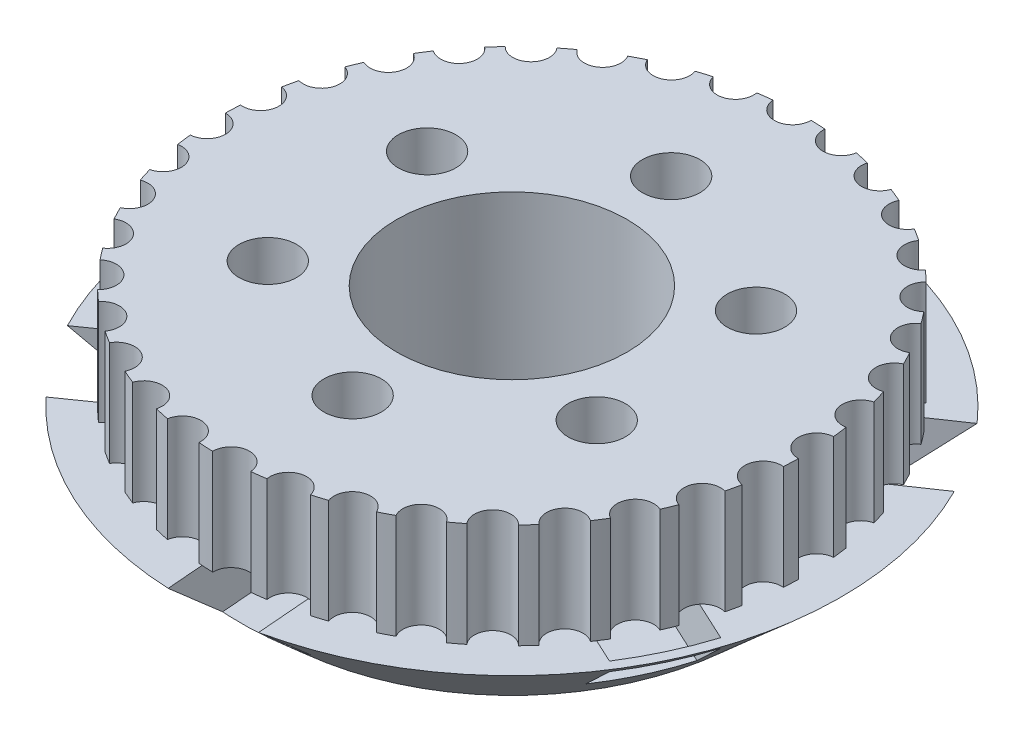
SolidWorks part; units mm, degrees
ref_plane "Front Plane" through (0, 0, 0) normal (0, 0, 1) x (1, 0, 0)
ref_plane "Top Plane" through (0, 0, 0) normal (0, 1, 0) x (1, 0, 0)
ref_plane "Right Plane" through (0, 0, 0) normal (1, 0, 0) x (0, 0, -1)
sketch "Sketch1" plane through (0, 0, 0) normal (0, 1, 0) x (1, 0, 0)
  circle A0 centre (0, 0) radius 28
  circle A1 centre (0, 0) radius 16.75 construction
  circle A2 centre (0, 0) radius 11
  circle A3 centre (-1.4643, 16.6859) radius 2.75
  circle A4 centre (13.7182, 9.611) radius 2.75
  circle A5 centre (15.1825, -7.0748) radius 2.75
  circle A6 centre (1.4643, -16.6859) radius 2.75
  circle A7 centre (-13.7182, -9.611) radius 2.75
  circle A8 centre (-15.1825, 7.0748) radius 2.75
  circle A9 centre (-24.8012, 12.9961) radius 1.75
  circle A10 centre (-22.1677, 17.1054) radius 1.75
  circle A11 centre (-18.8606, 20.6949) radius 1.75
  circle A12 centre (-14.9804, 23.6556) radius 1.75
  circle A13 centre (-10.6451, 25.8975) radius 1.75
  circle A14 centre (-5.9863, 27.3526) radius 1.75
  circle A15 centre (-1.1456, 27.9766) radius 1.75
  circle A16 centre (3.7298, 27.7505) radius 1.75
  circle A17 centre (8.492, 26.6812) radius 1.75
  circle A18 centre (12.9961, 24.8012) radius 1.75
  circle A19 centre (17.1054, 22.1677) radius 1.75
  circle A20 centre (20.6949, 18.8606) radius 1.75
  circle A21 centre (23.6556, 14.9804) radius 1.75
  circle A22 centre (25.8975, 10.6451) radius 1.75
  circle A23 centre (27.3526, 5.9863) radius 1.75
  circle A24 centre (27.9766, 1.1456) radius 1.75
  circle A25 centre (27.7505, -3.7298) radius 1.75
  circle A26 centre (26.6812, -8.492) radius 1.75
  circle A27 centre (24.8012, -12.9961) radius 1.75
  circle A28 centre (22.1677, -17.1054) radius 1.75
  circle A29 centre (18.8606, -20.6949) radius 1.75
  circle A30 centre (14.9804, -23.6556) radius 1.75
  circle A31 centre (10.6451, -25.8975) radius 1.75
  circle A32 centre (5.9863, -27.3526) radius 1.75
  circle A33 centre (1.1456, -27.9766) radius 1.75
  circle A34 centre (-3.7298, -27.7505) radius 1.75
  circle A35 centre (-8.492, -26.6812) radius 1.75
  circle A36 centre (-12.9961, -24.8012) radius 1.75
  circle A37 centre (-17.1054, -22.1677) radius 1.75
  circle A38 centre (-20.6949, -18.8606) radius 1.75
  circle A39 centre (-23.6556, -14.9804) radius 1.75
  circle A40 centre (-25.8975, -10.6451) radius 1.75
  circle A41 centre (-27.3526, -5.9863) radius 1.75
  circle A42 centre (-27.9766, -1.1456) radius 1.75
  circle A43 centre (-27.7505, 3.7298) radius 1.75
  circle A44 centre (-26.6812, 8.492) radius 1.75
  circle A45 centre (0, 0) radius 23 construction
  circle A46 centre (0, 0) radius 20 construction
  dimension "D1" = 56
  dimension "D2" = 22
  dimension "D3" = 33.5
  dimension "D4" = 5.5
  dimension "D6" = 3.5
  dimension "D8" = 46
  dimension "D9" = 40
  dimension "D5" = 6
  dimension "D7" = 36
extrude "Boss-Extrude1" add sketch "Sketch1" along normal blind 10 contours A44 A0 A43 A42 A41 A40 A39 A38 A37 A36 A35 A34 A33 A32 A31 A30 A29 A28 A27 A26 A25 A24 A23 A22 A21 A20 A19 region at (25.4369, 0, -1.0416)
sketch "Sketch2" plane through (0, 0, 0) normal (0, -1, 0) x (1, 0, 0)
  circle A1 centre (0, 0) radius 31.5
  circle A2 centre (0, 0) radius 11
  dimension "D1" = 63
  dimension "D2" = 22
ref_plane "Plane1" through (0, -8, 0) normal (0, -1, 0) x (-1, 0, 0)
sketch "Sketch4" plane through (0, 0, 0) normal (0, 1, 0) x (1, 0, 0)
  line L0 (-13.7182, -9.611) -> (-11.4231, -12.887)
  line L4 (-16.0134, -6.335) -> (-13.7182, -9.611)
  line L5 (-13.7182, -9.611) -> (-15.2116, -10.6573) construction
  line L6 (-6.0971, -9.1556) -> (-22.4771, -20.6315)
  line L7 (-10.6874, -2.6036) -> (-27.0674, -14.0795)
  line L8 (-10.9776, 0.7024) -> (-29.1059, 9.15)
  line L9 (-7.5985, 7.9538) -> (-25.7269, 16.4013)
  line L10 (-4.8805, 9.858) -> (-6.6289, 29.7815)
  line L11 (3.0889, 10.5574) -> (1.3405, 30.4808)
  line L12 (6.0971, 9.1556) -> (22.4771, 20.6315)
  line L13 (10.6874, 2.6036) -> (27.0674, 14.0795)
  line L14 (10.9776, -0.7024) -> (29.1059, -9.15)
  line L15 (7.5985, -7.9538) -> (25.7269, -16.4013)
  line L16 (4.8805, -9.858) -> (6.6289, -29.7815)
  line L17 (-3.0889, -10.5574) -> (-1.3405, -30.4808)
  line L18 (-5.6566, 18.7021) -> (-5.2413, 13.9703) construction
  line L19 (-5.449, 16.3362) -> (2.5204, 17.0356) construction
  line L20 (-1.4643, 16.6859) -> (0, 0) construction
  line L21 (-5.2413, 13.9703) -> (-1.0327, 11.768)
  line L22 (-5.6566, 18.7021) -> (-1.8959, 21.6037) construction
  line L23 (2.3128, 19.4015) -> (-1.8959, 21.6037) construction
  line L24 (2.3128, 19.4015) -> (2.728, 14.6696) construction
  line L25 (2.728, 14.6696) -> (-1.0327, 11.768)
  line L26 (17.7538, 7.5544) -> (13.8635, 4.8288) construction
  line L27 (13.1634, 14.1064) -> (9.2732, 11.3808) construction
  line L28 (13.1634, 14.1064) -> (17.5567, 12.3003) construction
  line L29 (17.7538, 7.5544) -> (17.5567, 12.3003) construction
  line L30 (13.8635, 4.8288) -> (9.4703, 6.6349)
  line L31 (9.2732, 11.3808) -> (9.4703, 6.6349)
  line L32 (15.2144, -11.7415) -> (10.9089, -9.7352) construction
  line L33 (18.5934, -4.4902) -> (14.2879, -2.4839) construction
  line L34 (18.5934, -4.4902) -> (19.2259, -9.1979) construction
  line L35 (15.2144, -11.7415) -> (19.2259, -9.1979) construction
  line L36 (10.9089, -9.7352) -> (10.2764, -5.0275)
  line L37 (14.2879, -2.4839) -> (10.2764, -5.0275)
  line L38 (-2.766, -19.1903) -> (-3.1812, -14.4585) construction
  line L39 (5.2034, -18.4909) -> (4.7881, -13.7591) construction
  line L40 (5.2034, -18.4909) -> (1.4426, -21.3925) construction
  line L41 (-2.766, -19.1903) -> (1.4426, -21.3925) construction
  line L42 (-3.1812, -14.4585) -> (0.5795, -11.5568)
  line L43 (4.7881, -13.7591) -> (0.5795, -11.5568)
  line L44 (-18.207, -7.3432) -> (-14.3168, -4.6176) construction
  line L45 (-13.6167, -13.8952) -> (-9.7264, -11.1696) construction
  line L46 (-13.6167, -13.8952) -> (-18.0099, -12.0891) construction
  line L47 (-18.207, -7.3432) -> (-18.0099, -12.0891) construction
  line L48 (-14.3168, -4.6176) -> (-9.9235, -6.4237)
  line L49 (-9.7264, -11.1696) -> (-9.9235, -6.4237)
  line L50 (-15.6676, 11.9527) -> (-11.3621, 9.9464) construction
  line L51 (-19.0466, 4.7013) -> (-14.7412, 2.695) construction
  line L52 (-19.0466, 4.7013) -> (-19.6791, 9.409) construction
  line L53 (-15.6676, 11.9527) -> (-19.6791, 9.409) construction
  line L54 (-11.3621, 9.9464) -> (-10.7296, 5.2387)
  line L55 (-14.7412, 2.695) -> (-10.7296, 5.2387)
  circle A0 centre (0, 0) radius 16.75 construction
  arc A1 (-25.7269, 16.4013) -> (-29.1059, 9.15) centre (0, 0) ccw
  arc A2 (-7.5985, 7.9538) -> (-10.9776, 0.7024) centre (0, 0) ccw
  arc A3 (1.3405, 30.4808) -> (-6.6289, 29.7815) centre (0, 0) ccw
  circle A5 centre (0, 0) radius 11 construction
  arc A6 (-10.6874, -2.6036) -> (-6.0971, -9.1556) centre (0, 0) ccw
  arc A7 (-27.0674, -14.0795) -> (-22.4771, -20.6315) centre (0, 0) ccw
  arc A8 (3.0889, 10.5574) -> (-4.8805, 9.858) centre (0, 0) ccw
  arc A9 (27.0674, 14.0795) -> (22.4771, 20.6315) centre (0, 0) ccw
  arc A10 (10.6874, 2.6036) -> (6.0971, 9.1556) centre (0, 0) ccw
  arc A11 (25.7269, -16.4013) -> (29.1059, -9.15) centre (0, 0) ccw
  arc A12 (7.5985, -7.9538) -> (10.9776, -0.7024) centre (0, 0) ccw
  arc A13 (-1.3405, -30.4808) -> (6.6289, -29.7815) centre (0, 0) ccw
  arc A14 (-3.0889, -10.5574) -> (4.8805, -9.858) centre (0, 0) ccw
  circle A16 centre (-1.4643, 16.6859) radius 2.75 construction
  circle A17 centre (-1.4643, 16.6859) radius 2.75
  point P48 (0, 0)
  point P49 (0, 0)
  dimension "D1" = 4
  dimension "D2" = 20
  dimension "D4" = 2.375
  dimension "D5" = 4.75
  dimension "D3" = 6
  dimension "D6" = 6
sketch "Sketch3" plane through (0, -8, 0) normal (0, -1, 0) x (-1, 0, 0)
  circle A0 centre (0, 0) radius 22.5
  circle A1 centre (0, 0) radius 11
  dimension "D1" = 22
  dimension "D2" = 45
loft "Loft2" add section "Sketch2" section "Sketch3" connector at (1.4641, 0, 31.466) connector at (0.0848, -8, 22.4998)
extrude "Cut-Extrude1" cut sketch "Sketch3<4>" against normal through all both and the other way through all contours A1 region at (0, -8, 0)
sketch "Sketch3<4>" plane through (0, -8, 0) normal (0, -1, 0) x (-1, 0, 0) same geometry as "Sketch3"
extrude "Cut-Extrude2" cut sketch "Sketch1<4>" against normal through all both and the other way through all contours A8 | A7 | A6 | A5 | A4 | A3
sketch "Sketch1<4>" plane through (0, 0, 0) normal (0, 1, 0) x (1, 0, 0) same geometry as "Sketch1"
sketch "Sketch5" plane through (0, 0, 0) normal (0, 1, 0) x (1, 0, 0)
  line L0 (2.7499, 14.4206) -> (3.0889, 10.5574)
  line L1 (-5.2195, 13.7212) -> (-4.8805, 9.858)
  line L2 (-11.897, 10.2349) -> (-7.5985, 7.9538)
  line L15 (-5.6347, 18.4531) -> (-5.2195, 13.7212) construction
  line L16 (-5.4271, 16.0872) -> (2.5423, 16.7865) construction
  line L17 (-1.4424, 16.4368) -> (0, 0) construction
  line L18 (-5.2195, 13.7212) -> (-1.0109, 11.519)
  line L19 (-5.6347, 18.4531) -> (-1.874, 21.3547) construction
  line L20 (2.3346, 19.1524) -> (-1.874, 21.3547) construction
  line L21 (2.3346, 19.1524) -> (2.7499, 14.4206) construction
  line L22 (2.7499, 14.4206) -> (-1.0109, 11.519)
  line L23 (17.3724, 6.9817) -> (13.3295, 4.0269) construction
  line L24 (12.7821, 13.5337) -> (8.8918, 10.8082) construction
  line L25 (12.7821, 13.5337) -> (17.1753, 11.7276) construction
  line L26 (17.3724, 6.9817) -> (17.1753, 11.7276) construction
  line L27 (13.3295, 4.0269) -> (9.089, 6.0623)
  line L28 (8.8918, 10.8082) -> (9.089, 6.0623)
  line L29 (15.4192, -11.5981) -> (11.1137, -9.5918) construction
  line L30 (18.7982, -4.3467) -> (14.4927, -2.3404) construction
  line L31 (18.7982, -4.3467) -> (19.4307, -9.0544) construction
  line L32 (15.4192, -11.5981) -> (19.4307, -9.0544) construction
  line L33 (11.1137, -9.5918) -> (10.4812, -4.8841)
  line L34 (14.4927, -2.3404) -> (10.4812, -4.8841)
  line L35 (-2.3346, -19.1524) -> (-2.7499, -14.4206) construction
  line L36 (5.6347, -18.4531) -> (5.2195, -13.7212) construction
  line L37 (5.6347, -18.4531) -> (1.874, -21.3547) construction
  line L38 (-2.3346, -19.1524) -> (1.874, -21.3547) construction
  line L39 (-2.7499, -14.4206) -> (1.0109, -11.519)
  line L40 (5.2195, -13.7212) -> (1.0109, -11.519)
  line L41 (-18.6318, -8.0111) -> (-14.7416, -5.2856) construction
  line L42 (-13.6975, -14.9083) -> (-9.8072, -12.1828) construction
  line L43 (-13.6975, -14.9083) -> (-18.4347, -12.757) construction
  line L44 (-18.6318, -8.0111) -> (-18.4347, -12.757) construction
  line L45 (-14.7416, -5.2856) -> (-10.3483, -7.0916)
  line L46 (-9.8072, -12.1828) -> (-10.3483, -7.0916)
  line L47 (-15.4192, 11.5981) -> (-11.897, 10.2349) construction
  line L48 (-18.7982, 4.3467) -> (-14.4927, 2.3404) construction
  line L49 (-18.7982, 4.3467) -> (-19.4307, 9.0544) construction
  line L50 (-15.4192, 11.5981) -> (-19.4307, 9.0544) construction
  line L51 (-11.897, 10.2349) -> (-10.4812, 4.8841)
  line L52 (-14.4927, 2.3404) -> (-10.4812, 4.8841)
  line L53 (-14.4927, 2.3404) -> (-10.9776, 0.7024)
  line L54 (-14.7416, -5.2856) -> (-11.5655, -3.0604)
  line L55 (-9.8072, -12.1828) -> (-6.6311, -9.9576)
  line L56 (-2.7499, -14.4206) -> (-3.0889, -10.5574)
  line L57 (5.2195, -13.7212) -> (4.8805, -9.858)
  line L58 (11.1137, -9.5918) -> (7.5985, -7.9538)
  line L59 (14.4927, -2.3404) -> (10.9776, -0.7024)
  line L60 (13.3295, 4.0269) -> (10.1534, 1.8017)
  line L61 (8.8918, 10.8082) -> (5.7157, 8.583)
  line L62 (-11.897, 10.2349) -> (-26.5615, 16.9334)
  line L63 (-30.0501, 9.4468) -> (-14.4927, 2.3404)
  line L64 (-27.9454, -14.5362) -> (-14.7416, -5.2856)
  line L65 (-23.0551, -21.4642) -> (-9.8072, -12.1828)
  line L66 (-1.384, -31.4696) -> (-2.7499, -14.4206)
  line L67 (6.588, -30.8034) -> (5.2195, -13.7212)
  line L68 (25.7269, -16.4013) -> (11.1137, -9.5918)
  line L69 (29.1059, -9.15) -> (14.4927, -2.3404)
  line L70 (28.1578, 14.1206) -> (13.3295, 4.0269)
  line L71 (23.624, 20.8365) -> (8.8918, 10.8082)
  line L72 (1.384, 31.4696) -> (2.7499, 14.4206)
  line L73 (-5.2195, 13.7212) -> (-6.7161, 30.7757)
  circle A0 centre (0, 0) radius 10.3426 construction
  arc A1 (-26.5615, 16.9334) -> (-30.0501, 9.4468) centre (0, 0) ccw
  arc A2 (-7.5985, 7.9538) -> (-10.9776, 0.7024) centre (0, 0) ccw
  arc A3 (1.384, 31.4696) -> (-6.7161, 30.7757) centre (0, 0) ccw
  arc A4 (-11.5655, -3.0604) -> (-6.6311, -9.9576) centre (0, 0) ccw
  arc A5 (-27.9454, -14.5362) -> (-23.0551, -21.4642) centre (0, 0) ccw
  arc A6 (3.0889, 10.5574) -> (-4.8805, 9.858) centre (0, 0) ccw
  arc A7 (28.1578, 14.1206) -> (23.624, 20.8365) centre (0, 0) ccw
  arc A8 (10.1534, 1.8017) -> (5.7157, 8.583) centre (0, 0) ccw
  arc A9 (25.7269, -16.4013) -> (29.1059, -9.15) centre (0, 0) ccw
  arc A10 (7.5985, -7.9538) -> (10.9776, -0.7024) centre (0, 0) ccw
  arc A11 (-1.384, -31.4696) -> (6.588, -30.8034) centre (0, 0) ccw
  arc A12 (-3.0889, -10.5574) -> (4.8805, -9.858) centre (0, 0) ccw
  circle A13 centre (-1.4424, 16.4368) radius 2.625 construction
  circle A14 centre (0, 0) radius 31.5 construction
extrude "Cut-Extrude5" cut sketch "Sketch5" against normal blind 5 contours L64 A5 L65 L46 L45 | L66 A11 L67 L40 L39 | L68 A9 L69 L34 L33 | L70 A7 L71 L28 L27 | L72 A3 L73 L18 L22 | L62 A1 L63 L52 L51 region at (-1.9056, 0, -22.0583) region at (-20.1387, 0, -9.4144) region at (18.0615, 0, -12.1445) region at (19.595, 0, 9.131) region at (1.8736, 0, 22.0355) region at (-18.4391, 0, 13.0488)
